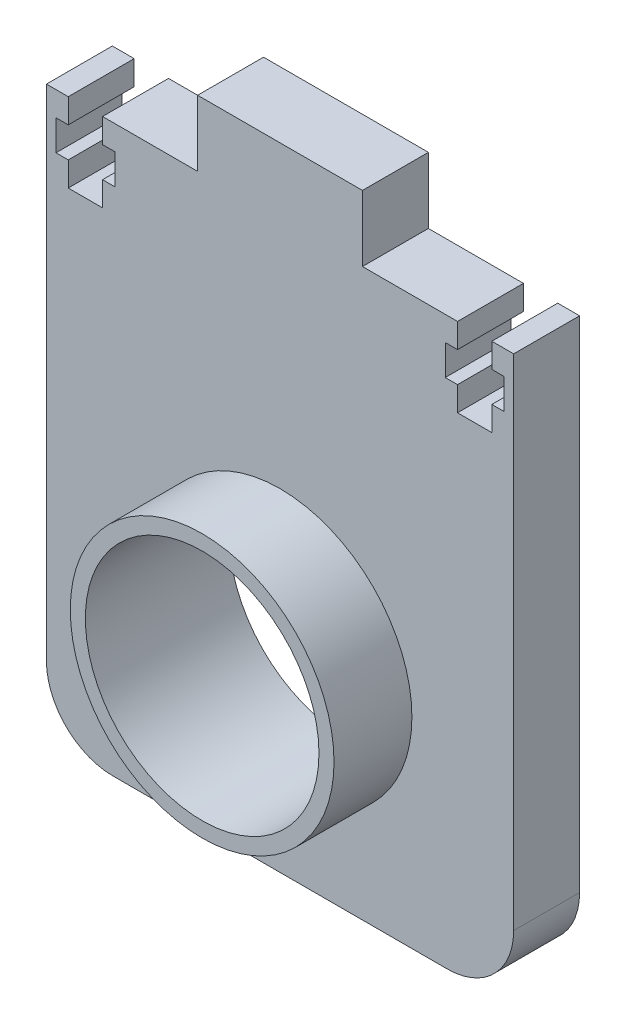
SolidWorks part; units mm, degrees
ref_plane "Front Plane" through (0, 0, 0) normal (0, 0, 1) x (1, 0, 0)
ref_plane "Top Plane" through (0, 0, 0) normal (0, 1, 0) x (1, 0, 0)
ref_plane "Right Plane" through (0, 0, 0) normal (1, 0, 0) x (0, 0, -1)
sketch "Sketch12" plane through (0, 0, 0) normal (0, 0, 1) x (1, 0, 0)
  line L0 (62.1258, 0) -> (62.1258, 121.71)
  line L1 (62.1258, 121.71) -> (152.1258, 121.71)
  line L2 (62.1258, 0) -> (152.1258, 0)
  line L3 (152.1258, 121.71) -> (152.1258, 0)
  line L4 (107.1258, 38.628) -> (107.1258, 121.71) construction
  circle A0 centre (107.1258, 38.628) radius 25.4
  circle A1 centre (107.1258, 38.628) radius 6.5
  dimension "D3" = 50.8
  dimension "D4" = 13
  dimension "D1" = 121.71
  dimension "D2" = 90
  dimension "D5" = 83.082
extrude "Boss-Extrude10" add sketch "Sketch12" along normal blind 12.7 separate body contours L1 L3 L2 L0
sketch "Sketch15" plane through (0, 0, 12.7) normal (0, 0, 1) x (1, 0, 0)
  line L0 (62.1258, 0) -> (152.1258, 0) construction
  circle A0 centre (107.1258, 38.6276) radius 25.4
  point P4 (107.1258, 0)
  dimension "D1" = 50.8
  dimension "D2" = 38.6276
extrude "Boss-Extrude11" add sketch "Sketch15" along normal blind 15
sketch "Sketch23" plane through (0, 0, 27.7) normal (0, 0, 1) x (1, 0, 0)
  circle A0 centre (107.1258, 38.6276) radius 22.5
  dimension "D1" = 45
extrude "Cut-Extrude7" cut sketch "Sketch23" against normal through all
fillet "Fillet2" radius 12.8 2 edges at (152.1258, 0, 6.35) (62.1258, 0, 6.35)
sketch "Sketch25" plane through (0, 0, 12.7) normal (0, 0, 1) x (1, 0, 0)
  line L0 (152.1258, 121.71) -> (152.1258, 109.01)
  line L1 (152.1258, 121.71) -> (152.1258, 12.8) construction
  line L2 (107.1258, 121.71) -> (107.1258, 98.7556)
  line L3 (62.1258, 12.8) -> (62.1258, 121.71) construction
  line L4 (62.1258, 109.01) -> (62.1258, 121.71)
  line L5 (123.0008, 109.01) -> (123.0008, 121.71)
  line L6 (62.1258, 121.71) -> (152.1258, 121.71) construction
  line L7 (123.0008, 121.71) -> (91.2508, 121.71)
  line L8 (91.2508, 121.71) -> (91.2508, 109.01)
  line L9 (91.2508, 109.01) -> (107.1258, 109.01)
  line L10 (107.1258, 109.01) -> (123.0008, 109.01)
  line L11 (152.1258, 109.01) -> (123.0008, 109.01)
  line L12 (123.0008, 121.71) -> (91.2508, 121.71)
  line L13 (91.2508, 109.01) -> (62.1258, 109.01)
  line M10 (152.1258, 12.8) -> (152.1258, 121.71)
  line M11 (152.1258, 121.71) -> (62.1258, 121.71)
  line M12 (62.1258, 121.71) -> (62.1258, 12.8)
  dimension "D1" = 12.7
  dimension "D2" = 31.75
extrude "Cut-Extrude9" cut sketch "Sketch25" against normal through all contours L13 L8 M11 M12 | L11 L5 M10 M11 region at (137.5633, 115.36, 12.7) region at (76.6883, 115.36, 12.7)
sketch "Sketch27" plane through (0, 0, 12.7) normal (0, 0, 1) x (1, 0, 0)
  line L0 (147.9178, 109.01) -> (147.9178, 104.311)
  line L1 (152.1258, 109.01) -> (123.0008, 109.01) construction
  line L2 (147.9178, 104.311) -> (150.2798, 104.311)
  line L3 (150.2798, 104.311) -> (150.2798, 98.469)
  line L4 (150.2798, 98.469) -> (147.9178, 98.469)
  line L5 (147.9178, 98.469) -> (147.9178, 93.77)
  line L6 (147.9178, 93.77) -> (141.3138, 93.77)
  line L7 (141.3138, 93.77) -> (141.3138, 98.469)
  line L8 (141.3138, 98.469) -> (138.9518, 98.469)
  line L9 (138.9518, 98.469) -> (138.9518, 104.311)
  line L10 (138.9518, 104.311) -> (141.3138, 104.311)
  line L11 (141.3138, 104.311) -> (141.3138, 109.01)
  line L12 (107.1258, 121.71) -> (107.1258, 67.6415) construction
  line L13 (91.2508, 121.71) -> (123.0008, 121.71) construction
  line L14 (72.9378, 98.469) -> (75.2998, 98.469)
  line L15 (75.2998, 98.469) -> (75.2998, 104.311)
  line L16 (75.2998, 104.311) -> (72.9378, 104.311)
  line L17 (72.9378, 104.311) -> (72.9378, 109.01)
  line L18 (66.3338, 109.01) -> (66.3338, 104.311)
  line L19 (66.3338, 104.311) -> (63.9718, 104.311)
  line L20 (63.9718, 104.311) -> (63.9718, 98.469)
  line L21 (63.9718, 98.469) -> (66.3338, 98.469)
  line L22 (66.3338, 98.469) -> (66.3338, 93.77)
  line L23 (66.3338, 93.77) -> (72.9378, 93.77)
  line L24 (72.9378, 93.77) -> (72.9378, 98.469)
  line L25 (147.9178, 109.01) -> (141.3138, 109.01)
  line L26 (72.9378, 109.01) -> (66.3338, 109.01)
  point P30 (144.6158, 109.01)
  point P31 (69.6358, 109.01)
  dimension "D1" = 6.604
  dimension "D2" = 11.328
  dimension "D3" = 15.24
  dimension "D4" = 5.842
  dimension "D5" = 74.98
ref_axis "Axis1" through (107.1258, 121.71, 12.7) along (0, -1, 0)
extrude "Cut-Extrude10" cut sketch "Sketch27" against normal through all
